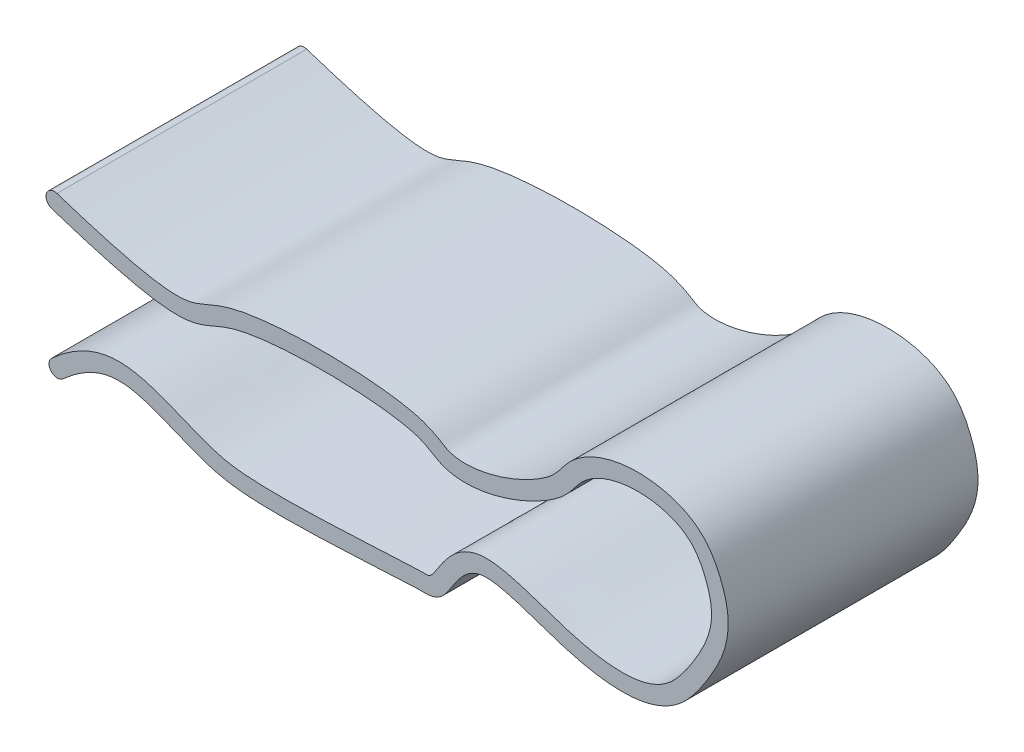
SolidWorks part; units mm, degrees
ref_plane "Front Plane" through (0, 0, 0) normal (0, 0, 1) x (1, 0, 0)
ref_plane "Top Plane" through (0, 0, 0) normal (0, 1, 0) x (1, 0, 0)
ref_plane "Right Plane" through (0, 0, 0) normal (1, 0, 0) x (0, 0, -1)
sketch "Sketch1" plane through (0, 0, 0) normal (0, 0, 1) x (1, 0, 0)
  line L0 (0, 0) -> (15, 0)
  line L1 (0, 4) -> (15, 4)
  line L2 (15, 0) -> (15, -2)
  line L3 (15, -2) -> (0, -2)
  line L4 (0, 0) -> (0, -2)
  line L5 (15, 4) -> (15, 6)
  line L6 (15, 6) -> (0, 6)
  line L7 (0, 6) -> (0, 4)
  line L8 (-4.7792, 6.5899) -> (-4.7792, 5.3738)
  line L9 (-9.6674, 7.8303) -> (-10.2456, 6.7524)
  arc A0 (-11.245, -2.8913) -> (-12.0485, -2) centre (-11.6467, -2.4457) cw
  arc A1 (-12.0485, 7.3249) -> (-11.6761, 8.4656) centre (-11.8623, 7.8952) cw
  arc A2 (19.3292, 1.1717) -> (19.3827, -0.0295) centre (19.2762, 0.5676) cw
  arc A3 (-6.939, 0.2082) -> (-6.9982, -0.9904) centre (-6.9686, -0.3911) ccw
  arc A4 (16.7783, 6.4332) -> (16.7831, 5.201) centre (16.5555, 5.8162) cw
  arc A5 (-2.1526, 5.2736) -> (-2.2467, 6.4731) centre (-2.2556, 5.8689) cw
  spline S0 degree 3 poles (-12.0485, -2) (-7.5701, 2.0369) (-4.4175, -0.7066) (2.8122, -2.8428) (14.3319, -1.8691) (15.6308, -2.1509) (17.0848, 2.755) (30.0193, -2.6571) (33.042, 0.4363) (35.2278, 3.7871) (36.185, 5.9433) (33.2739, 11.1975) (27.062, 11.2763) (24.4598, 6.7436) (17.3677, 3.948) (13.8686, 7.1489) (-2.553, 7.333) (-1.3833, 3.8434) (-12.0485, 7.3249) knots 0 0 0 0 0.088285 0.098847 0.148924 0.160301 0.206352 0.233111 0.316348 0.349994 0.54517 0.587692 0.732689 0.763169 0.862015 0.881989 0.942932 1 1 1 1
  spline S1 degree 1 poles (-11.245, -2.8913) (-11.6761, 8.4656) knots 0 0 1 1 construction
  spline S2 degree 3 poles (-11.245, -2.8913) (-11.0719, -2.7353) (-10.7043, -2.4219) (-10.0376, -1.9227) (-9.2603, -1.4609) (-8.4271, -1.1372) (-7.7548, -1.0066) (-7.2194, -0.9795) (-6.711, -1.0015) (-5.8317, -1.132) (-4.7306, -1.4878) (-3.4721, -1.9932) (-2.4601, -2.4105) (-1.3667, -2.8253) (-0.1982, -3.231) (1.4997, -3.5214) (3.6888, -3.6062) (6.1829, -3.5842) (8.7626, -3.4881) (11.191, -3.3628) (12.887, -3.2683) (13.9183, -3.219) (14.4899, -3.2021) (14.8011, -3.2033) (15.1245, -3.2144) (15.5905, -3.1) (16.0342, -2.8471) (16.3116, -2.5371) (16.5441, -2.2189) (16.7501, -1.8989) (16.9583, -1.5765) (17.2523, -1.1512) (17.6648, -0.6608) (18.2264, -0.2411) (18.756, -0.0602) (19.2203, -0.0239) (19.5574, -0.0337) (20.2265, -0.1134) (21.4522, -0.4261) (23.1551, -1.0084) (25.4518, -1.7855) (27.8822, -2.287) (30.1833, -2.2846) (31.9824, -1.7777) (33.277, -0.9293) (34.0961, -0.027) (34.5898, 0.6304) (34.9781, 1.2087) (35.2821, 1.6981) (35.68, 2.3633) (36.1185, 3.198) (36.5178, 4.2671) (36.7193, 5.4318) (36.661, 6.6718) (36.3753, 7.7527) (36.0196, 8.6308) (35.6547, 9.3626) (35.123, 10.135) (34.0779, 11.0944) (32.4439, 11.8014) (30.2469, 12.0946) (28.3697, 11.8726) (26.9506, 11.3772) (26.1229, 10.9131) (25.5242, 10.4451) (24.9625, 9.881) (24.4983, 9.234) (23.9896, 8.6633) (23.0087, 7.9575) (21.7082, 7.2759) (20.2474, 6.7168) (18.7753, 6.3607) (17.685, 6.2897) (17.1152, 6.3561) (16.8482, 6.4126) (16.7006, 6.4542) (16.473, 6.5368) (16.2393, 6.662) (15.5514, 7.098) (14.456, 7.5495) (13.0212, 7.8472) (11.3166, 8.0562) (8.7718, 8.2189) (6.0191, 8.2119) (3.4548, 8.02) (1.7273, 7.7826) (0.2428, 7.4119) (-0.8311, 6.9513) (-1.4986, 6.661) (-2.0037, 6.512) (-2.5564, 6.4189) (-3.3161, 6.398) (-4.2727, 6.5034) (-4.9428, 6.617) (-5.5616, 6.7349) (-6.4594, 6.9325) (-7.8369, 7.2904) (-9.0432, 7.64) (-9.9756, 7.9241) (-10.7032, 8.1511) (-11.3281, 8.352) (-11.6761, 8.4656) knots 0 0 0 0 0.003906 0.007812 0.015625 0.023438 0.03125 0.03609 0.039996 0.046875 0.0625 0.070312 0.078125 0.085938 0.09375 0.101562 0.109375 0.117188 0.125 0.132812 0.140625 0.144531 0.148438 0.152344 0.15625 0.158203 0.160156 0.164062 0.167969 0.171875 0.175781 0.179688 0.1875 0.195312 0.203125 0.205878 0.207832 0.210938 0.21875 0.226562 0.234375 0.25 0.265625 0.28125 0.296875 0.3125 0.328125 0.34375 0.359375 0.375 0.40625 0.4375 0.46875 0.5 0.53125 0.546875 0.5625 0.578125 0.59375 0.625 0.65625 0.6875 0.703125 0.71875 0.726562 0.734375 0.75 0.765625 0.78125 0.796875 0.8125 0.828125 0.84375 0.851264 0.853217 0.857124 0.859375 0.867188 0.875 0.882812 0.890625 0.898438 0.90625 0.921875 0.929688 0.9375 0.945312 0.953125 0.960938 0.965761 0.969668 0.976562 0.981529 0.983482 0.984458 0.988281 0.992188 0.995617 0.996594 0.998047 1 1 1 1
  point P37 (19.3292, 1.1717)
  point P38 (19.3827, -0.0295)
  point P42 (-10.2456, -0.9904)
  point P44 (-9.1694, -0.9904)
  dimension "D2" = 4
  dimension "D1" = 15
  dimension "D3" = 2
  dimension "D4" = 1.2
extrude "Boss-Extrude3" add sketch "Sketch1" along normal blind 18 contours S0 A1 S2 A0
ref_plane "Plane3" through (0, 0, -2) normal (0, 0, -1) x (-1, 0, 0)
sketch "Sketch6" plane through (0, 0, -2) normal (0, 0, -1) x (-1, 0, 0)
  arc A0 (-19.3292, 1.1717) -> (-19.3827, -0.0295) centre (-19.2762, 0.5676) ccw
  arc A1 (6.9982, -0.9904) -> (6.939, 0.2082) centre (6.9686, -0.3911) ccw
  spline S0 degree 3 poles (-19.3292, 1.1717) (-16.6711, 1.3924) (-3.2331, -1.2852) (6.939, 0.2082) knots 0 0 0 0 1 1 1 1
  spline S1 degree 3 poles (-19.3827, -0.0295) (-10.6509, -1.1156) (-6.8585, -2.2109) (6.9982, -0.9904) knots 0 0 0 0 1 1 1 1
